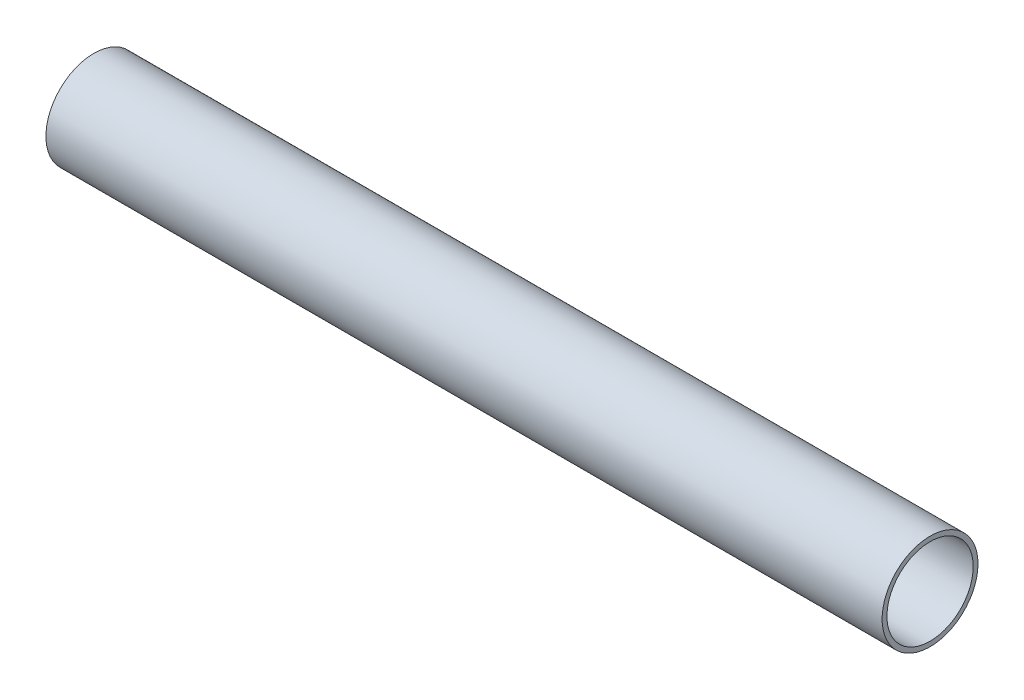
SolidWorks part; units mm, degrees
material "PC High Viscosity"
ref_plane "Front Plane" through (0, 0, 0) normal (0, 0, 1) x (1, 0, 0)
ref_plane "Top Plane" through (0, 0, 0) normal (0, 1, 0) x (1, 0, 0)
ref_plane "Right Plane" through (0, 0, 0) normal (1, 0, 0) x (0, 0, -1)
sketch "Sketch1" plane through (0, 0, 0) normal (1, 0, 0) x (0, 0, -1)
  circle A0 centre (0, 0) radius 15.875
  dimension "D1" = 31.75
extrude "Extrude-Thin1" add sketch "Sketch1" along normal mid plane 276.927 thin thin type one direction reverse wall 1.5875
